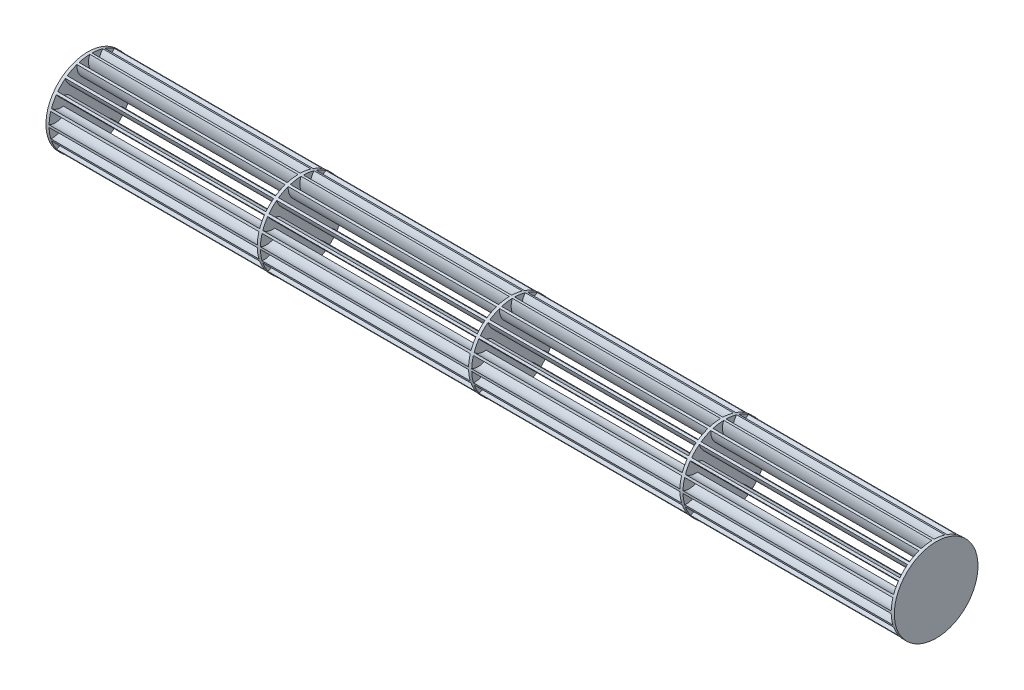
SolidWorks part; units mm, degrees
ref_plane "Front Plane" through (0, 0, 0) normal (0, 0, 1) x (1, 0, 0)
ref_plane "Top Plane" through (0, 0, 0) normal (0, 1, 0) x (1, 0, 0)
ref_plane "Right Plane" through (0, 0, 0) normal (1, 0, 0) x (0, 0, -1)
ref_plane "Plane2" through (202, 0, 0) normal (1, 0, 0) x (0, 0, -1)
sketch "Sketch2" plane through (202, 0, 0) normal (1, 0, 0) x (0, 0, -1)
  circle A0 centre (0, 0) radius 20
  dimension "D1" = 40
extrude "Boss-Extrude2" add sketch "Sketch2" against normal blind 1.5
sketch "Sketch1" plane through (0, 0, 0) normal (1, 0, 0) x (0, 0, -1)
  line L0 (-0.5459, 19.9925) -> (0.5459, 19.9925) construction
  arc A0 (0.5459, 19.9925) -> (-0.5459, 19.9925) centre (0, 0) ccw
  arc A1 (0.5459, 19.9925) -> (0.5459, 13.9894) centre (6.8697, 16.991) ccw
  arc A2 (-0.5459, 19.9925) -> (-0.5459, 13.9894) centre (6.8697, 16.991) ccw
  arc A3 (0.5459, 13.9894) -> (-0.5459, 13.9894) centre (0, 0) ccw
  arc A4 (-0.5459, 19.9925) -> (0.5459, 19.9925) centre (0, 0) ccw construction
  point P3 (5.8839, 16.9904)
  point P4 (67.2495, 16.9924)
  point P11 (0, 14)
  dimension "D1" = 40
  dimension "D4" = 8
  dimension "D2" = 1
  dimension "D3" = 6
extrude "Boss-Extrude1" add sketch "Sketch1" along normal mid plane 404
pattern_circular "CirPattern1" count 20 over 360 about axis through (202, 0, 0) along (1, 0, 0) of "Boss-Extrude1"
pattern_linear "LPattern1" count 5 spacing 101 along (-1, 0, 0) of "Boss-Extrude2"
equation "\"A\"= 420mm"
equation "\"num_segments\"= 4"
equation "\"end_clearance\"= 8mm"
equation "\"impeller_diameter\"= 40mm"
equation "\"D1@Sketch1\"=\"impeller_diameter\""
equation "\"D1@Boss-Extrude1\"=\"A\"-(2*\"end_clearance\")"
equation "\"D1@Plane2\"=(\"A\"/2)-\"end_clearance\""
equation "\"D1@Sketch2\"=\"impeller_diameter\""
equation "\"D1@LPattern1\"=\"num_segments\"+1"
